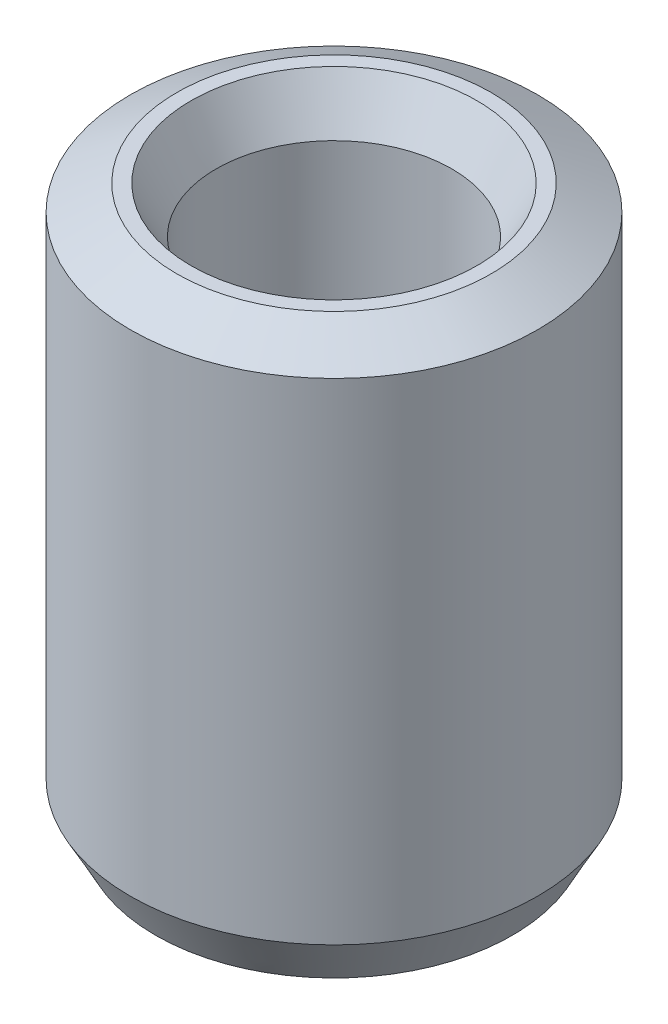
SolidWorks part; units mm, degrees
ref_plane "Front Plane" through (0, 0, 0) normal (0, 0, 1) x (1, 0, 0)
ref_plane "Top Plane" through (0, 0, 0) normal (0, 1, 0) x (1, 0, 0)
ref_plane "Right Plane" through (0, 0, 0) normal (1, 0, 0) x (0, 0, -1)
sketch "Sketch1" plane through (0, 0, 0) normal (0, 1, 0) x (1, 0, 0)
  circle A0 centre (0, 0) radius 30
  dimension "SLEEVE_OD" = 60
extrude "Boss-Extrude1" add sketch "Sketch1" along normal blind 82.8378
sketch "Sketch2" plane through (0, 0, 0) normal (0, 1, 0) x (1, 0, 0)
  circle A0 centre (0, 0) radius 17.3596
  dimension "BORE_D" = 34.7192
extrude "Cut-Extrude1" cut sketch "Sketch2" along normal through all
chamfer "Chamfer1" distance 3.7092 angle 61.548 4 edges at (0, 82.8378, 17.3596) (0, 0, 17.3596) (0, 0, 30) (0, 82.8378, 30) first distance on face at (0, 82.8378, 17.3596) first distance on face at (0, 0, 17.3596) first distance on face at (0, 82.8378, 30)
